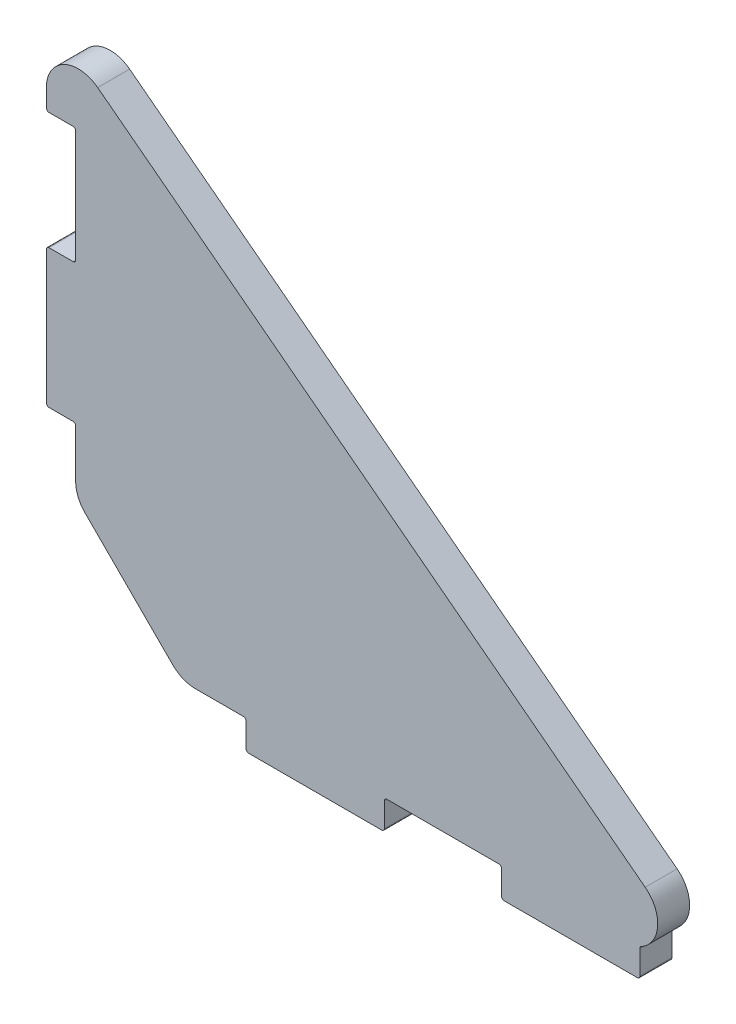
SolidWorks part; units mm, degrees
material "Plain Carbon Steel"
ref_plane "Front" through (0, 0, 0) normal (0, 0, 1) x (1, 0, 0)
ref_plane "Top" through (0, 0, 0) normal (0, 1, 0) x (1, 0, 0)
ref_plane "Right" through (0, 0, 0) normal (1, 0, 0) x (0, 0, -1)
sketch "Sketch1" plane through (0, 0, 0) normal (0, 0, 1) x (1, 0, 0)
  line L5 (-4.3656, 76.2) -> (95.25, 0)
  line L6 (15.875, 0) -> (25.4, 0)
  line L7 (0, 15.875) -> (0, 25.4)
  line L10 (46.0375, 0) -> (63.5, 0)
  line L12 (25.4, 0) -> (25.4, -4.3656)
  line L13 (25.4, -4.3656) -> (46.0375, -4.3656)
  line L14 (46.0375, 0) -> (46.0375, -4.3656)
  line L16 (63.5, 0) -> (63.5, -4.3656)
  line L17 (63.5, -4.3656) -> (84.1375, -4.3656)
  line L18 (84.1375, 0) -> (84.1375, -4.3656)
  line L19 (84.1375, 0) -> (95.25, 0)
  line L20 (0, 46.0375) -> (0, 63.5)
  line L23 (0, 63.5) -> (-4.3656, 63.5)
  line L24 (-4.3656, 76.2) -> (-4.3656, 63.5)
  line L25 (0, 46.0375) -> (-4.3656, 46.0375)
  line L27 (0, 25.4) -> (-4.3656, 25.4)
  line L28 (-4.3656, 46.0375) -> (-4.3656, 25.4)
  line L30 (0, 15.875) -> (15.875, 0)
  point P0 (-4.3656, 76.2)
  dimension "D1" = 20.6375
  dimension "D2" = 38.1
  dimension "D4" = 38.1
  dimension "D5" = 9.525
  dimension "D6" = 25.4
  dimension "D7" = 25.4
  dimension "D8" = 76.2
  dimension "D9" = 95.25
base flange "Base-Flange1" sketch "Sketch1" thickness 4.7625 reverse thickness direction no parameters "D1"=0.7366
fillet "Fillet1" radius 0.3969 14 edges at (46.0375, 0, -2.3813) (63.5, 0, -2.3813) (63.5, -4.3656, -2.3813) (84.1375, -4.3656, -2.3813) (84.1375, 0, -2.3813) (-4.3656, 63.5, -2.3813) (0, 63.5, -2.3813) (0, 46.0375, -2.3813) (-4.3656, 46.0375, -2.3813) (-4.3656, 25.4, -2.3813) (0, 25.4, -2.3813) (46.0375, -4.3656, -2.3813) (25.4, 0, -2.3813) (25.4, -4.3656, -2.3813)
fillet "Fillet2" radius 4.7625 4 edges at (95.25, 0, -2.3813) (15.875, 0, -2.3813) (0, 15.875, -2.3813) (-4.3656, 76.2, -2.3813)
sketch "Bend-Lines1" [suppressed] plane through (0, 0, 0) normal (0, 1, 0) x (1, 0, 0)
sketch "Bounding-Box1" [suppressed] plane through (0, 0, 0) normal (0, 1, 0) x (1, 0, 0)
sheet metal parameters "Sheet-Metal28" thickness 4.7625 parameters "D1"=0.7366
flat pattern "Flat-Pattern28" [suppressed]
sketch "Bend-Lines2" plane through (0, 0, 0) normal (0, 1, 0) x (1, 0, 0)
sketch3d "Bounding-Box2" [suppressed]
  line L0 (-0.4923, 73.2371, 0) -> (90.2183, 3.849, 0) construction
  line L1 (-29.6596, 35.1068, 0) -> (61.0509, -34.2813, 0) construction
  line L2 (-0.4923, 73.2371, 0) -> (-29.6596, 35.1068, 0) construction
  line L3 (90.2183, 3.849, 0) -> (61.0509, -34.2813, 0) construction
equation "\"Total Cutting Length\"= \"Cutting Length-Outer\" + \"Cutting Length-Inner\""
equation "\"Amount in ft^2\"= \"Bounding Box Area-Blank\" / 144"
